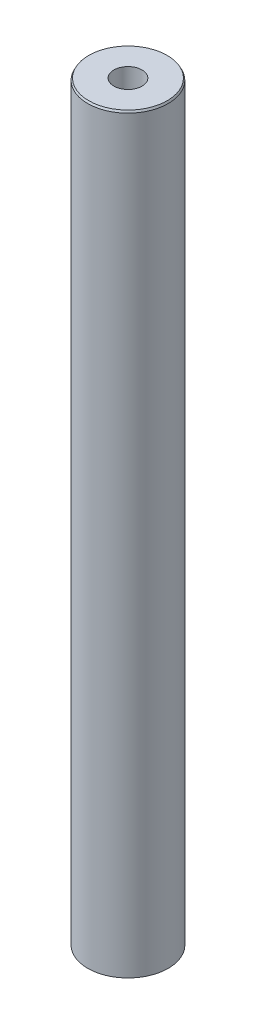
SolidWorks part; units mm, degrees
ref_plane "Front Plane" through (0, 0, 0) normal (0, 0, 1) x (1, 0, 0)
ref_plane "Top Plane" through (0, 0, 0) normal (0, 1, 0) x (1, 0, 0)
ref_plane "Right Plane" through (0, 0, 0) normal (1, 0, 0) x (0, 0, -1)
sketch "Sketch1" plane through (0, 0, 0) normal (0, 1, 0) x (1, 0, 0)
  circle A0 centre (0, 0) radius 5
  dimension "SHAFT_OD" = 10
extrude "Boss-Extrude1" add sketch "Sketch1" along normal blind 93.4415
sketch "Sketch2" plane through (0, 0, 0) normal (0, 1, 0) x (1, 0, 0)
  circle A0 centre (0, 0) radius 1.7482
  dimension "BORE_D" = 3.4964
extrude "Cut-Extrude1" cut sketch "Sketch2" along normal through all
chamfer "Chamfer1" distance 0.2458 angle 26.527 2 edges at (0, 93.4415, 5) (0, 0, 5) first distance on face at (0, 93.4415, 5) first distance on face at (0, 0, 1.7482)
